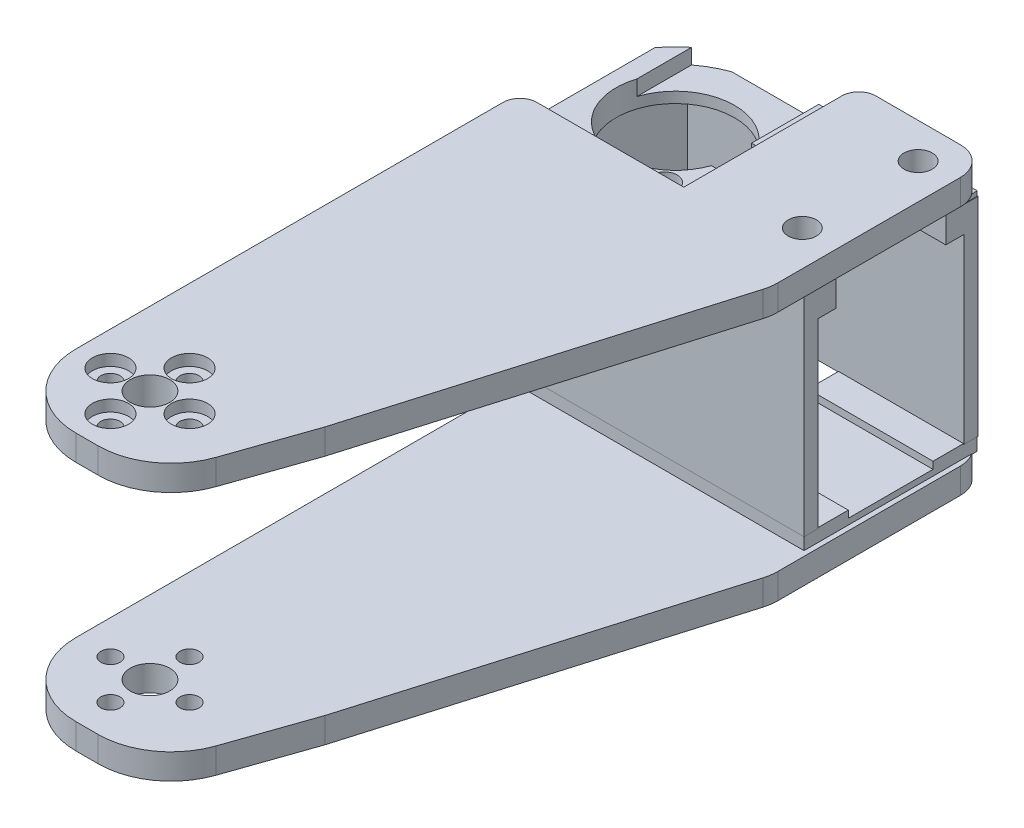
SolidWorks part; units mm, degrees
ref_plane "Front Plane" through (0, 0, 0) normal (0, 0, 1) x (1, 0, 0)
ref_plane "Top Plane" through (0, 0, 0) normal (0, 1, 0) x (1, 0, 0)
ref_plane "Right Plane" through (0, 0, 0) normal (1, 0, 0) x (0, 0, -1)
ref_plane "PY_m23_300" through (0, -23.3, 0) normal (0, 1, 0) x (1, 0, 0)
sketch "S_prism1" plane through (0, -23.3, 0) normal (0, 1, 0) x (1, 0, 0)
  line L0 (-0.1, -13) -> (3.8289, -13)
  line L1 (16.0129, -4.3379) -> (21, 10)
  line L2 (21, 10) -> (38.6729, 69.8916)
  line L3 (39, 72.1557) -> (39, 104.5)
  line L4 (34, 109.5) -> (19, 109.5)
  line L5 (16, 106.5) -> (16, 78.5)
  line L6 (16, 78.5) -> (-10, 78.5)
  line L7 (-13, 75.5) -> (-13, -0.1)
  arc A0 (-13, -0.1) -> (-0.1, -13) centre (-0.1001, -0.1001) ccw
  arc A1 (3.8289, -13) -> (16.0129, -4.3379) centre (3.8289, -0.1) ccw
  arc A2 (38.6729, 69.8916) -> (39, 72.1557) centre (31.0004, 72.1557) ccw
  arc A3 (39, 104.5) -> (34, 109.5) centre (33.9999, 104.4999) ccw
  arc A4 (19, 109.5) -> (16, 106.5) centre (19.0001, 106.4999) ccw
  arc A5 (-10, 78.5) -> (-13, 75.5) centre (-9.9999, 75.4999) ccw
extrude "Boss_1" add sketch "S_prism1" along normal blind 4.5
ref_plane "PY_p17_750" through (0, 17.75, 0) normal (0, 1, 0) x (1, 0, 0)
sketch "S_cyl2" plane through (0, 17.75, 0) normal (0, 1, 0) x (1, 0, 0)
  circle A0 centre (0, 0) radius 9.5
  dimension "D1_S_cyl2" = 19
extrude "Boss_2" add sketch "S_cyl2" along normal blind 3.2
ref_plane "PY_p20_950" through (0, 20.95, 0) normal (0, 1, 0) x (1, 0, 0)
sketch "S_prism3" plane through (0, 20.95, 0) normal (0, 1, 0) x (1, 0, 0)
  line L0 (-0.1, -13) -> (3.8289, -13)
  line L1 (16.0129, -4.3379) -> (21, 10)
  line L2 (21, 10) -> (38.6729, 69.8916)
  line L3 (39, 72.1557) -> (39, 104.5)
  line L4 (34, 109.5) -> (19, 109.5)
  line L5 (16, 106.5) -> (16, 78.5)
  line L6 (16, 78.5) -> (-10, 78.5)
  line L7 (-13, 75.5) -> (-13, -0.1)
  arc A0 (-13, -0.1) -> (-0.1, -13) centre (-0.1001, -0.1001) ccw
  arc A1 (3.8289, -13) -> (16.0129, -4.3379) centre (3.8289, -0.1) ccw
  arc A2 (38.6729, 69.8916) -> (39, 72.1557) centre (31.0004, 72.1557) ccw
  arc A3 (39, 104.5) -> (34, 109.5) centre (33.9999, 104.4999) ccw
  arc A4 (19, 109.5) -> (16, 106.5) centre (19.0001, 106.4999) ccw
  arc A5 (-10, 78.5) -> (-13, 75.5) centre (-9.9999, 75.4999) ccw
extrude "Boss_3" add sketch "S_prism3" along normal blind 4.5
ref_plane "PZ_m108_400" through (0, 0, -108.4) normal (0, 0, 1) x (1, 0, 0)
sketch "S_box4" plane through (0, 0, -108.4) normal (0, 0, 1) x (1, 0, 0)
  line L0 (-13.2, -16.6) -> (-10.7, -16.6)
  line L1 (-10.7, -16.6) -> (-10.7, 20.2)
  line L2 (-10.7, 20.2) -> (-13.2, 20.2)
  line L3 (-13.2, 20.2) -> (-13.2, -16.6)
  dimension "P1" = 13.2
  dimension "P2" = 16.6
  dimension "P3" = 10.7
  dimension "P4" = 16.6
  dimension "P5" = 10.7
  dimension "P6" = 20.2
  dimension "P7" = 13.2
  dimension "P8" = 20.2
extrude "Boss_4" add sketch "S_box4" along normal blind 30.8
sketch "S_box5" plane through (0, 0, -108.4) normal (0, 0, 1) x (1, 0, 0)
  line L0 (-13.2, -16.6) -> (38.2, -16.6)
  line L1 (38.2, -16.6) -> (38.2, 20.2)
  line L2 (38.2, 20.2) -> (-13.2, 20.2)
  line L3 (-13.2, 20.2) -> (-13.2, -16.6)
  dimension "P1" = 13.2
  dimension "P2" = 16.6
  dimension "P3" = 38.2
  dimension "P4" = 16.6
  dimension "P5" = 38.2
  dimension "P6" = 20.2
  dimension "P7" = 13.2
  dimension "P8" = 20.2
extrude "Boss_5" add sketch "S_box5" along normal blind 2.5
ref_plane "PZ_m80_100" through (0, 0, -80.1) normal (0, 0, 1) x (1, 0, 0)
sketch "S_box6" plane through (0, 0, -80.1) normal (0, 0, 1) x (1, 0, 0)
  line L0 (-13.2, -16.6) -> (38.2, -16.6)
  line L1 (38.2, -16.6) -> (38.2, 20.2)
  line L2 (38.2, 20.2) -> (-13.2, 20.2)
  line L3 (-13.2, 20.2) -> (-13.2, -16.6)
  dimension "P1" = 13.2
  dimension "P2" = 16.6
  dimension "P3" = 38.2
  dimension "P4" = 16.6
  dimension "P5" = 38.2
  dimension "P6" = 20.2
  dimension "P7" = 13.2
  dimension "P8" = 20.2
extrude "Boss_6" add sketch "S_box6" along normal blind 2.5
sketch "S_box7" plane through (0, 0, -108.4) normal (0, 0, 1) x (1, 0, 0)
  line L0 (-13.2, 15.6) -> (38.2, 15.6)
  line L1 (38.2, 15.6) -> (38.2, 20.2)
  line L2 (38.2, 20.2) -> (-13.2, 20.2)
  line L3 (-13.2, 20.2) -> (-13.2, 15.6)
  dimension "P1" = 13.2
  dimension "P2" = 15.6
  dimension "P3" = 38.2
  dimension "P4" = 15.6
  dimension "P5" = 38.2
  dimension "P6" = 20.2
  dimension "P7" = 13.2
  dimension "P8" = 20.2
extrude "Boss_7" add sketch "S_box7" along normal blind 30.8
ref_plane "PZ_m108_330" through (0, 0, -108.33) normal (0, 0, 1) x (1, 0, 0)
sketch "S_box8" plane through (0, 0, -108.33) normal (0, 0, 1) x (1, 0, 0)
  line L0 (16, -18.9) -> (38.13, -18.9)
  line L1 (38.13, -18.9) -> (38.13, -16.5)
  line L2 (38.13, -16.5) -> (16, -16.5)
  line L3 (16, -16.5) -> (16, -18.9)
  dimension "P1" = 16
  dimension "P2" = 18.9
  dimension "P3" = 38.13
  dimension "P4" = 18.9
  dimension "P5" = 38.13
  dimension "P6" = 16.5
  dimension "P7" = 16
  dimension "P8" = 16.5
extrude "Boss_8" add sketch "S_box8" along normal blind 30.66
ref_plane "PZ_m79_500" through (0, 0, -79.5) normal (0, 0, 1) x (1, 0, 0)
sketch "S_box9" plane through (0, 0, -79.5) normal (0, 0, 1) x (1, 0, 0)
  line L0 (-13.13, -18.9) -> (16.03, -18.9)
  line L1 (16.03, -18.9) -> (16.03, -16.5)
  line L2 (16.03, -16.5) -> (-13.13, -16.5)
  line L3 (-13.13, -16.5) -> (-13.13, -18.9)
  dimension "P1" = 13.13
  dimension "P2" = 18.9
  dimension "P3" = 16.03
  dimension "P4" = 18.9
  dimension "P5" = 16.03
  dimension "P6" = 16.5
  dimension "P7" = 13.13
  dimension "P8" = 16.5
extrude "Boss_9" add sketch "S_box9" along normal blind 1.83
sketch "S_box10" plane through (0, 0, -108.33) normal (0, 0, 1) x (1, 0, 0)
  line L0 (16, 20.1) -> (38.13, 20.1)
  line L1 (38.13, 20.1) -> (38.13, 21.05)
  line L2 (38.13, 21.05) -> (16, 21.05)
  line L3 (16, 21.05) -> (16, 20.1)
  dimension "P1" = 16
  dimension "P2" = 20.1
  dimension "P3" = 38.13
  dimension "P4" = 20.1
  dimension "P5" = 38.13
  dimension "P6" = 21.05
  dimension "P7" = 16
  dimension "P8" = 21.05
extrude "Boss_10" add sketch "S_box10" along normal blind 30.66
sketch "S_box11" plane through (0, 0, -79.5) normal (0, 0, 1) x (1, 0, 0)
  line L0 (-13.13, 20.1) -> (16.03, 20.1)
  line L1 (16.03, 20.1) -> (16.03, 21.05)
  line L2 (16.03, 21.05) -> (-13.13, 21.05)
  line L3 (-13.13, 21.05) -> (-13.13, 20.1)
  dimension "P1" = 13.13
  dimension "P2" = 20.1
  dimension "P3" = 16.03
  dimension "P4" = 20.1
  dimension "P5" = 16.03
  dimension "P6" = 21.05
  dimension "P7" = 13.13
  dimension "P8" = 21.05
extrude "Boss_11" add sketch "S_box11" along normal blind 1.83
ref_plane "PY_m23_400" through (0, -23.4, 0) normal (0, 1, 0) x (1, 0, 0)
sketch "S_hole12" plane through (0, -23.4, 0) normal (0, 1, 0) x (1, 0, 0)
  circle A0 centre (0, 0) radius 3.5
  dimension "D1_S_hole12" = 7
extrude "Hole_12" cut sketch "S_hole12" along normal blind 4.7
sketch "S_hole13" plane through (0, -23.4, 0) normal (0, 1, 0) x (1, 0, 0)
  circle A0 centre (7, 0) radius 1.7
  dimension "D1_S_hole13" = 3.4
  dimension "P2" = 7
extrude "Hole_13" cut sketch "S_hole13" along normal blind 4.7
sketch "S_hole14" plane through (0, -23.4, 0) normal (0, 1, 0) x (1, 0, 0)
  circle A0 centre (0, -7) radius 1.7
  dimension "D1_S_hole14" = 3.4
  dimension "P2" = 7
extrude "Hole_14" cut sketch "S_hole14" along normal blind 4.7
sketch "S_hole15" plane through (0, -23.4, 0) normal (0, 1, 0) x (1, 0, 0)
  circle A0 centre (-7, 0) radius 1.7
  dimension "D1_S_hole15" = 3.4
  dimension "P2" = 7
extrude "Hole_15" cut sketch "S_hole15" along normal blind 4.7
sketch "S_hole16" plane through (0, -23.4, 0) normal (0, 1, 0) x (1, 0, 0)
  circle A0 centre (0, 7) radius 1.7
  dimension "D1_S_hole16" = 3.4
  dimension "P2" = 7
extrude "Hole_16" cut sketch "S_hole16" along normal blind 4.7
sketch "S_hole17" plane through (0, -23.4, 0) normal (0, 1, 0) x (1, 0, 0)
  circle A0 centre (7, 0) radius 3.2
  dimension "D1_S_hole17" = 6.4
  dimension "P2" = 7
extrude "Hole_17" cut sketch "S_hole17" along normal blind 1.6
sketch "S_hole18" plane through (0, -23.4, 0) normal (0, 1, 0) x (1, 0, 0)
  circle A0 centre (0, -7) radius 3.2
  dimension "D1_S_hole18" = 6.4
  dimension "P2" = 7
extrude "Hole_18" cut sketch "S_hole18" along normal blind 1.6
sketch "S_hole19" plane through (0, -23.4, 0) normal (0, 1, 0) x (1, 0, 0)
  circle A0 centre (-7, 0) radius 3.2
  dimension "D1_S_hole19" = 6.4
  dimension "P2" = 7
extrude "Hole_19" cut sketch "S_hole19" along normal blind 1.6
sketch "S_hole20" plane through (0, -23.4, 0) normal (0, 1, 0) x (1, 0, 0)
  circle A0 centre (0, 7) radius 3.2
  dimension "D1_S_hole20" = 6.4
  dimension "P2" = 7
extrude "Hole_20" cut sketch "S_hole20" along normal blind 1.6
ref_plane "PY_p17_650" through (0, 17.65, 0) normal (0, 1, 0) x (1, 0, 0)
sketch "S_hole21" plane through (0, 17.65, 0) normal (0, 1, 0) x (1, 0, 0)
  circle A0 centre (0, 0) radius 3.5
  dimension "D1_S_hole21" = 7
extrude "Hole_21" cut sketch "S_hole21" along normal blind 7.9
sketch "S_hole22" plane through (0, 17.65, 0) normal (0, 1, 0) x (1, 0, 0)
  circle A0 centre (7, 0) radius 1.7
  dimension "D1_S_hole22" = 3.4
  dimension "P2" = 7
extrude "Hole_22" cut sketch "S_hole22" along normal blind 7.9
sketch "S_hole23" plane through (0, 17.65, 0) normal (0, 1, 0) x (1, 0, 0)
  circle A0 centre (0, -7) radius 1.7
  dimension "D1_S_hole23" = 3.4
  dimension "P2" = 7
extrude "Hole_23" cut sketch "S_hole23" along normal blind 7.9
sketch "S_hole24" plane through (0, 17.65, 0) normal (0, 1, 0) x (1, 0, 0)
  circle A0 centre (-7, 0) radius 1.7
  dimension "D1_S_hole24" = 3.4
  dimension "P2" = 7
extrude "Hole_24" cut sketch "S_hole24" along normal blind 7.9
sketch "S_hole25" plane through (0, 17.65, 0) normal (0, 1, 0) x (1, 0, 0)
  circle A0 centre (0, 7) radius 1.7
  dimension "D1_S_hole25" = 3.4
  dimension "P2" = 7
extrude "Hole_25" cut sketch "S_hole25" along normal blind 7.9
ref_plane "PY_p23_450" through (0, 23.45, 0) normal (0, 1, 0) x (1, 0, 0)
sketch "S_hole26" plane through (0, 23.45, 0) normal (0, 1, 0) x (1, 0, 0)
  circle A0 centre (7, 0) radius 3.2
  dimension "D1_S_hole26" = 6.4
  dimension "P2" = 7
extrude "Hole_26" cut sketch "S_hole26" along normal blind 2.1
sketch "S_hole27" plane through (0, 23.45, 0) normal (0, 1, 0) x (1, 0, 0)
  circle A0 centre (0, -7) radius 3.2
  dimension "D1_S_hole27" = 6.4
  dimension "P2" = 7
extrude "Hole_27" cut sketch "S_hole27" along normal blind 2.1
sketch "S_hole28" plane through (0, 23.45, 0) normal (0, 1, 0) x (1, 0, 0)
  circle A0 centre (-7, 0) radius 3.2
  dimension "D1_S_hole28" = 6.4
  dimension "P2" = 7
extrude "Hole_28" cut sketch "S_hole28" along normal blind 2.1
sketch "S_hole29" plane through (0, 23.45, 0) normal (0, 1, 0) x (1, 0, 0)
  circle A0 centre (0, 7) radius 3.2
  dimension "D1_S_hole29" = 6.4
  dimension "P2" = 7
extrude "Hole_29" cut sketch "S_hole29" along normal blind 2.1
sketch "S_cut30" plane through (0, 0, 0) normal (0, 0, 1) x (1, 0, 0)
  line L0 (-3.4, 17.65) -> (3.4, 17.65)
  line L1 (3.4, 17.65) -> (3.4, 18.65)
  line L2 (3.4, 18.65) -> (-3.4, 18.65)
  line L3 (-3.4, 18.65) -> (-3.4, 17.65)
  dimension "P1" = 3.4
  dimension "P2" = 17.65
  dimension "P3" = 3.4
  dimension "P4" = 17.65
  dimension "P5" = 3.4
  dimension "P6" = 18.65
  dimension "P7" = 3.4
  dimension "P8" = 18.65
extrude "Pocket_30" cut sketch "S_cut30" along normal blind 10
ref_plane "PY_p15_500" through (0, 15.5, 0) normal (0, 1, 0) x (1, 0, 0)
sketch "S_hole31" plane through (0, 15.5, 0) normal (0, 1, 0) x (1, 0, 0)
  circle A0 centre (0, 93) radius 10.5
  dimension "D1_S_hole31" = 21
  dimension "P2" = 93
extrude "Hole_31" cut sketch "S_hole31" along normal blind 4.8
ref_plane "PZ_m102_700" through (0, 0, -102.7) normal (0, 0, 1) x (1, 0, 0)
sketch "S_cut32" plane through (0, 0, -102.7) normal (0, 0, 1) x (1, 0, 0)
  line L0 (10.9, 15.55) -> (30.4, 15.55)
  line L1 (30.4, 15.55) -> (30.4, 20.3)
  line L2 (30.4, 20.3) -> (10.9, 20.3)
  line L3 (10.9, 20.3) -> (10.9, 15.55)
  dimension "P1" = 10.9
  dimension "P2" = 15.55
  dimension "P3" = 30.4
  dimension "P4" = 15.55
  dimension "P5" = 30.4
  dimension "P6" = 20.3
  dimension "P7" = 10.9
  dimension "P8" = 20.3
extrude "Pocket_32" cut sketch "S_cut32" along normal blind 19.4
sketch "S_cut33" plane through (0, 0, -102.7) normal (0, 0, 1) x (1, 0, 0)
  line L0 (30.4, 15.55) -> (38.7, 15.55)
  line L1 (38.7, 15.55) -> (38.7, 20.3)
  line L2 (38.7, 20.3) -> (30.4, 20.3)
  line L3 (30.4, 20.3) -> (30.4, 15.55)
  dimension "P1" = 30.4
  dimension "P2" = 15.55
  dimension "P3" = 38.7
  dimension "P4" = 15.55
  dimension "P5" = 38.7
  dimension "P6" = 20.3
  dimension "P7" = 30.4
  dimension "P8" = 20.3
extrude "Pocket_33" cut sketch "S_cut33" along normal blind 19.4
ref_plane "PZ_m96_500" through (0, 0, -96.5) normal (0, 0, 1) x (1, 0, 0)
sketch "S_cut34" plane through (0, 0, -96.5) normal (0, 0, 1) x (1, 0, 0)
  line L0 (0, 15.55) -> (11, 15.55)
  line L1 (11, 15.55) -> (11, 20.3)
  line L2 (11, 20.3) -> (0, 20.3)
  line L3 (0, 20.3) -> (0, 15.55)
  dimension "P1" = 15.55
  dimension "P2" = 11
  dimension "P3" = 15.55
  dimension "P4" = 11
  dimension "P5" = 20.3
  dimension "P6" = 20.3
extrude "Pocket_34" cut sketch "S_cut34" along normal blind 7
ref_plane "PZ_m108_900" through (0, 0, -108.9) normal (0, 0, 1) x (1, 0, 0)
sketch "S_cut35" plane through (0, 0, -108.9) normal (0, 0, 1) x (1, 0, 0)
  line L0 (-10, 17.5) -> (10, 17.5)
  line L1 (10, 17.5) -> (10, 20.4)
  line L2 (10, 20.4) -> (-10, 20.4)
  line L3 (-10, 20.4) -> (-10, 17.5)
  dimension "P1" = 10
  dimension "P2" = 17.5
  dimension "P3" = 10
  dimension "P4" = 17.5
  dimension "P5" = 10
  dimension "P6" = 20.4
  dimension "P7" = 10
  dimension "P8" = 20.4
extrude "Pocket_35" cut sketch "S_cut35" along normal blind 15.9
sketch "S_hole36" plane through (0, 15.5, 0) normal (0, 1, 0) x (1, 0, 0)
  circle A0 centre (8.3, 82.75) radius 1.1
  dimension "D1_S_hole36" = 2.2
  dimension "P2" = 8.3
  dimension "P3" = 82.75
extrude "Hole_36" cut sketch "S_hole36" along normal blind 4.8
ref_plane "PY_p18_600" through (0, 18.6, 0) normal (0, 1, 0) x (1, 0, 0)
sketch "S_hole37" plane through (0, 18.6, 0) normal (0, 1, 0) x (1, 0, 0)
  circle A0 centre (8.3, 82.75) radius 2.3
  dimension "D1_S_hole37" = 4.6
  dimension "P2" = 8.3
  dimension "P3" = 82.75
extrude "Hole_37" cut sketch "S_hole37" along normal blind 1.7
sketch "S_hole38" plane through (0, 15.5, 0) normal (0, 1, 0) x (1, 0, 0)
  circle A0 centre (32.75, 103.25) radius 1.1
  dimension "D1_S_hole38" = 2.2
  dimension "P2" = 32.75
  dimension "P3" = 103.25
extrude "Hole_38" cut sketch "S_hole38" along normal blind 4.8
sketch "S_hole39" plane through (0, 18.6, 0) normal (0, 1, 0) x (1, 0, 0)
  circle A0 centre (32.75, 103.25) radius 2.3
  dimension "D1_S_hole39" = 4.6
  dimension "P2" = 32.75
  dimension "P3" = 103.25
extrude "Hole_39" cut sketch "S_hole39" along normal blind 1.7
sketch "S_hole40" plane through (0, 15.5, 0) normal (0, 1, 0) x (1, 0, 0)
  circle A0 centre (32.75, 82.75) radius 1.1
  dimension "D1_S_hole40" = 2.2
  dimension "P2" = 32.75
  dimension "P3" = 82.75
extrude "Hole_40" cut sketch "S_hole40" along normal blind 4.8
sketch "S_hole41" plane through (0, 18.6, 0) normal (0, 1, 0) x (1, 0, 0)
  circle A0 centre (32.75, 82.75) radius 2.3
  dimension "D1_S_hole41" = 4.6
  dimension "P2" = 32.75
  dimension "P3" = 82.75
extrude "Hole_41" cut sketch "S_hole41" along normal blind 1.7
ref_plane "PZ_m100_500" through (0, 0, -100.5) normal (0, 0, 1) x (1, 0, 0)
sketch "S_cut42" plane through (0, 0, -100.5) normal (0, 0, 1) x (1, 0, 0)
  line L0 (8.1, -17.75) -> (38.7, -17.75)
  line L1 (38.7, -17.75) -> (38.7, -16.2)
  line L2 (38.7, -16.2) -> (8.1, -16.2)
  line L3 (8.1, -16.2) -> (8.1, -17.75)
  dimension "P1" = 8.1
  dimension "P2" = 17.75
  dimension "P3" = 38.7
  dimension "P4" = 17.75
  dimension "P5" = 38.7
  dimension "P6" = 16.2
  dimension "P7" = 8.1
  dimension "P8" = 16.2
extrude "Pocket_42" cut sketch "S_cut42" along normal blind 15
ref_plane "PY_p20_250" through (0, 20.25, 0) normal (0, 1, 0) x (1, 0, 0)
sketch "S_hole43" plane through (0, 20.25, 0) normal (0, 1, 0) x (1, 0, 0)
  circle A0 centre (32.75, 103.25) radius 2.5
  dimension "D1_S_hole43" = 5
  dimension "P2" = 32.75
  dimension "P3" = 103.25
extrude "Hole_43" cut sketch "S_hole43" along normal blind 5.3
sketch "S_hole44" plane through (0, 20.25, 0) normal (0, 1, 0) x (1, 0, 0)
  circle A0 centre (32.75, 82.75) radius 2.5
  dimension "D1_S_hole44" = 5
  dimension "P2" = 32.75
  dimension "P3" = 82.75
extrude "Hole_44" cut sketch "S_hole44" along normal blind 5.3
sketch "S_pcut45" plane through (0, 15.5, 0) normal (0, 1, 0) x (1, 0, 0)
  line L0 (0.5, 109.308) -> (0.5, 113)
  line L1 (0.5, 113) -> (-20, 113)
  line L2 (-20, 113) -> (-20, 93)
  line L3 (-20, 93) -> (-16.3, 93)
  arc A0 (-16.3, 93) -> (0.5, 109.308) centre (0.0258, 92.9891) cw
extrude "Cut_45" cut sketch "S_pcut45" along normal blind 4.9
ref_plane "PY_m16_400" through (0, -16.4, 0) normal (0, 1, 0) x (1, 0, 0)
sketch "S_pcut46" plane through (0, -16.4, 0) normal (0, 1, 0) x (1, 0, 0)
  line L0 (0.5, 111.508) -> (0.5, 113)
  line L1 (0.5, 113) -> (-20, 113)
  line L2 (-20, 113) -> (-20, 93)
  line L3 (-20, 93) -> (-18.5, 93)
  arc A0 (-18.5, 93) -> (0.5, 111.508) centre (0.0245, 92.9896) cw
extrude "Cut_46" cut sketch "S_pcut46" along normal blind 32
equation "\"plate_t\" = 3"
equation "\"clearance\" = 0.5"
